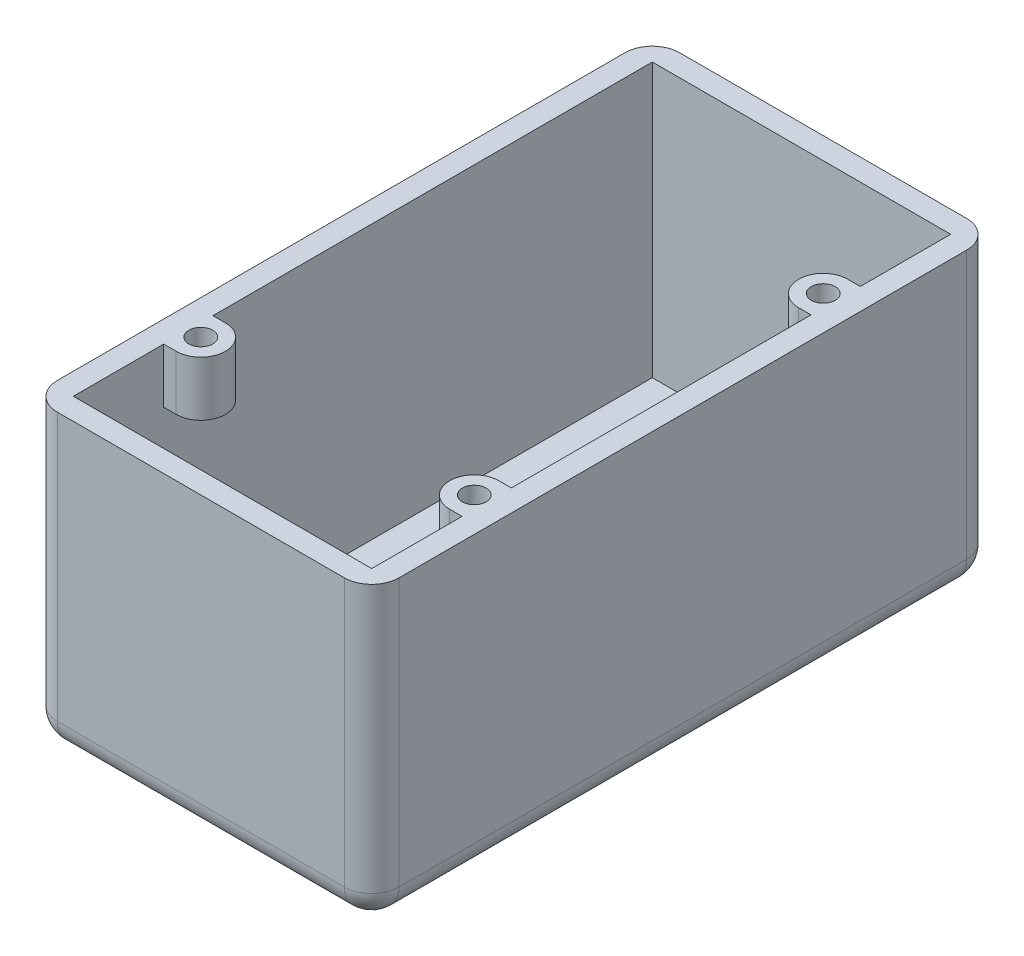
SolidWorks part; units mm, degrees
ref_plane "Front Plane" through (0, 0, 0) normal (0, 0, 1) x (1, 0, 0)
ref_plane "Top Plane" through (0, 0, 0) normal (0, 1, 0) x (1, 0, 0)
ref_plane "Right Plane" through (0, 0, 0) normal (1, 0, 0) x (0, 0, -1)
sketch "Sketch1" plane through (0, 0, 0) normal (0, 1, 0) x (1, 0, 0)
  line L1 (-25, 45.525) -> (25, 45.525)
  line L2 (-25, 45.525) -> (-25, -45.525)
  line L3 (-25, -45.525) -> (25, -45.525)
  line L4 (25, 45.525) -> (25, -45.525)
  line L5 (-25, 45.525) -> (25, -45.525) construction
  line L6 (-25, -45.525) -> (25, 45.525) construction
  line L7 (-21.825, 42.35) -> (21.825, 42.35)
  line L8 (-21.825, 42.35) -> (-21.825, -42.35)
  line L9 (-21.825, -42.35) -> (21.825, -42.35)
  line L10 (21.825, 42.35) -> (21.825, -42.35)
  line L11 (-21.825, 42.35) -> (21.825, -42.35) construction
  line L12 (-21.825, -42.35) -> (21.825, 42.35) construction
  point P0 (0, 0)
  point P6 (0, 0)
  dimension "D1" = 3.175
  dimension "D2" = 3.175
  dimension "D3" = 91.05
  dimension "D4" = 50
extrude "Boss-Extrude1" add sketch "Sketch1" along normal blind 40
sketch "Sketch2" plane through (0, 0, 0) normal (0, -1, 0) x (1, 0, 0)
  line L1 (25, -45.525) -> (-25, -45.525)
  line L2 (25, -45.525) -> (25, 45.525)
  line L3 (25, 45.525) -> (-25, 45.525)
  line L4 (-25, -45.525) -> (-25, 45.525)
extrude "Boss-Extrude2" add sketch "Sketch2" along normal blind 3.175
fillet "Fillet1" radius 4 8 edges at (25, 18.4125, 45.525) (25, 18.4125, -45.525) (-25, 18.4125, -45.525) (-25, 18.4125, 45.525) (0, -3.175, 45.525) (-25, -3.175, 0) (0, -3.175, -45.525) (25, -3.175, 0)
sketch "Sketch3" plane through (0, 0, 0) normal (0, 1, 0) x (1, 0, 0)
  line L0 (-21.825, -42.35) -> (21.825, -42.35) construction
  line L1 (-15, 35.7) -> (8.05, 35.7) construction
  line L2 (-15, 35.7) -> (-15, -22.35) construction
  line L3 (-15, -22.35) -> (8.05, -22.35) construction
  line L4 (8.05, 35.7) -> (8.05, -22.35) construction
  line L6 (-21, -41.525) -> (-21, 41.525) construction
  circle A0 centre (-15, 35.7) radius 1.3
  circle A1 centre (8.05, 35.7) radius 1.3
  circle A2 centre (8.05, -22.35) radius 1.3
  circle A3 centre (-15, -22.35) radius 1.3
  dimension "D2" = 2.6
  dimension "D1" = 58.05
  dimension "D3" = 23.05
  dimension "D4" = 20
  dimension "D5" = 6
extrude "Cut-Extrude1" cut sketch "Sketch3" against normal up to surface (3.175 mm away) up to face at (0, -3.175, 0)
sketch "Sketch4" plane through (0, 40, 0) normal (0, 1, 0) x (1, 0, 0)
  line L0 (-20, -21.925) -> (-21.825, -21.925)
  line L1 (-21.825, 42.35) -> (-21.825, -42.35) construction
  line L2 (-21.825, -21.925) -> (-21.825, -29.125)
  line L3 (-21.825, -29.125) -> (-20, -29.125)
  line L4 (0, -45.525) -> (0, 45.525) construction
  line L5 (-21, -45.525) -> (21, -45.525) construction
  line L6 (21, 45.525) -> (-21, 45.525) construction
  line L7 (-25, 41.525) -> (-25, -41.525) construction
  line L8 (21.825, -29.125) -> (20, -29.125)
  line L9 (21.825, -21.925) -> (21.825, -29.125)
  line L10 (20, -21.925) -> (21.825, -21.925)
  line L11 (-25, 0) -> (25, 0) construction
  line L12 (25, -41.525) -> (25, 41.525) construction
  line L13 (20, 21.925) -> (21.825, 21.925)
  line L14 (21.825, 21.925) -> (21.825, 29.125)
  line L15 (21.825, 29.125) -> (20, 29.125)
  arc A0 (-20, -29.125) -> (-20, -21.925) centre (-20, -25.525) ccw
  arc A1 (20, -29.125) -> (20, -21.925) centre (20, -25.525) cw
  arc A2 (20, 29.125) -> (20, 21.925) centre (20, 25.525) ccw
  dimension "D1" = 7.2
  dimension "D2" = 5
  dimension "D3" = 20
extrude "Boss-Extrude3" add sketch "Sketch4" against normal blind 8
sketch "Sketch5" plane through (0, 40, 0) normal (0, 1, 0) x (1, 0, 0)
  line L0 (0, 45.525) -> (0, -45.525) construction
  line L1 (21, 45.525) -> (-21, 45.525) construction
  line L2 (-21, -45.525) -> (21, -45.525) construction
  line L3 (-25, 0) -> (25, 0) construction
  line L4 (-25, 41.525) -> (-25, -41.525) construction
  line L5 (25, -41.525) -> (25, 41.525) construction
  circle A0 centre (-20, -25.525) radius 1.75
  circle A1 centre (20, -25.525) radius 1.75
  circle A2 centre (20, 25.525) radius 1.75
  dimension "D1" = 3.5
extrude "Cut-Extrude2" cut sketch "Sketch5" against normal blind 5
